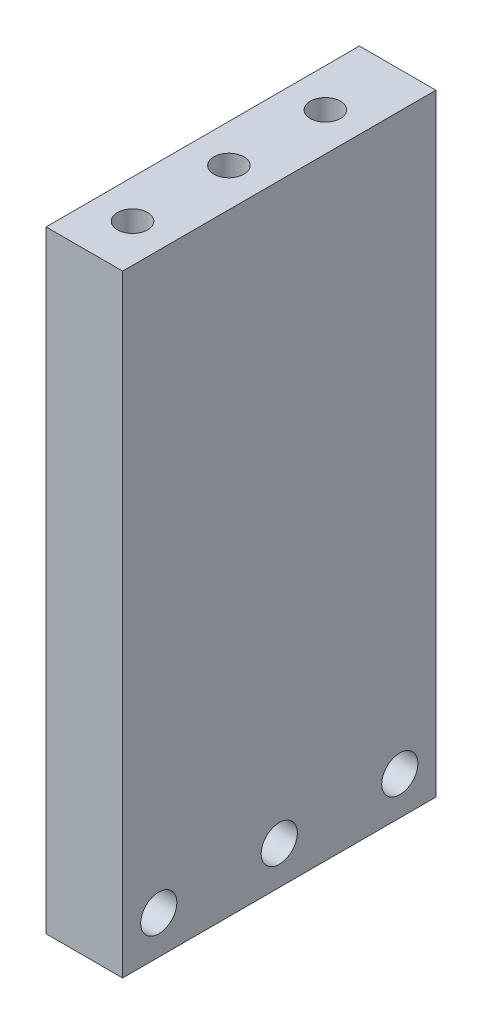
SolidWorks part; units mm, degrees
ref_plane "Front Plane" through (0, 0, 0) normal (0, 0, 1) x (1, 0, 0)
ref_plane "Top Plane" through (0, 0, 0) normal (0, 1, 0) x (1, 0, 0)
ref_plane "Right Plane" through (0, 0, 0) normal (1, 0, 0) x (0, 0, -1)
sketch "Sketch1" plane through (0, 0, 0) normal (0, 0, 1) x (1, 0, 0)
  line L1 (0, 0) -> (6.35, 0)
  line L2 (0, 0) -> (0, 50.8)
  line L3 (0, 50.8) -> (6.35, 50.8)
  line L4 (6.35, 0) -> (6.35, 50.8)
extrude "Boss-Extrude1" add sketch "Sketch1" along normal blind 26
sketch "Sketch4" plane through (6.35, 0, 0) normal (1, 0, 0) x (0, 0, -1)
  line L0 (0, 0) -> (0, 50.8) construction
  line L1 (-26, 0) -> (-26, 50.8) construction
  line L2 (-26, 0) -> (0, 0) construction
  circle A0 centre (-3, 3.175) radius 1.5
  circle A1 centre (-23, 3.175) radius 1.5
  dimension "D1" = 3
  dimension "D2" = 3
  dimension "D3" = 3
  dimension "D4" = 3
  dimension "D5" = 3.175
  dimension "D6" = 3.175
extrude "Cut-Extrude3" cut sketch "Sketch4" against normal blind 6.35
sketch "Sketch6" plane through (0, 0, 0) normal (-1, 0, 0) x (0, 0, 1)
  line L0 (26, 0) -> (0, 0) construction
  circle A0 centre (13, 3.175) radius 1.5
  circle A1 centre (3, 3.175) radius 1.5 construction
  dimension "D1" = 3
  dimension "D2" = 10
  dimension "D3" = 3.175
extrude "Cut-Extrude5" cut sketch "Sketch6" against normal blind 6.35
sketch "Sketch9" plane through (0, 50.8, 0) normal (0, 1, 0) x (1, 0, 0)
  circle A6 centre (3.175, -6) radius 1.25
  circle A7 centre (3.175, -14) radius 1.25
  circle A8 centre (3.175, -22) radius 1.25
sketch "Sketch12" plane through (0, 50.8, 0) normal (0, 1, 0) x (1, 0, 0)
  circle A0 centre (3.175, -6) radius 1.25
  circle A1 centre (3.175, -14) radius 1.25
  circle A2 centre (3.175, -22) radius 1.25
  dimension "D1" = 2.5
  dimension "D2" = 2.5
  dimension "D3" = 2.5
extrude "Cut-Extrude9" cut sketch "Sketch9" against normal blind 5 contours A6
extrude "Cut-Extrude10" cut sketch "Sketch12" against normal blind 5 contours A1
extrude "Cut-Extrude11" cut sketch "Sketch12<3>" against normal blind 5 contours A2
sketch "Sketch12<3>" plane through (0, 50.8, 0) normal (0, 1, 0) x (1, 0, 0) same geometry as "Sketch12"
